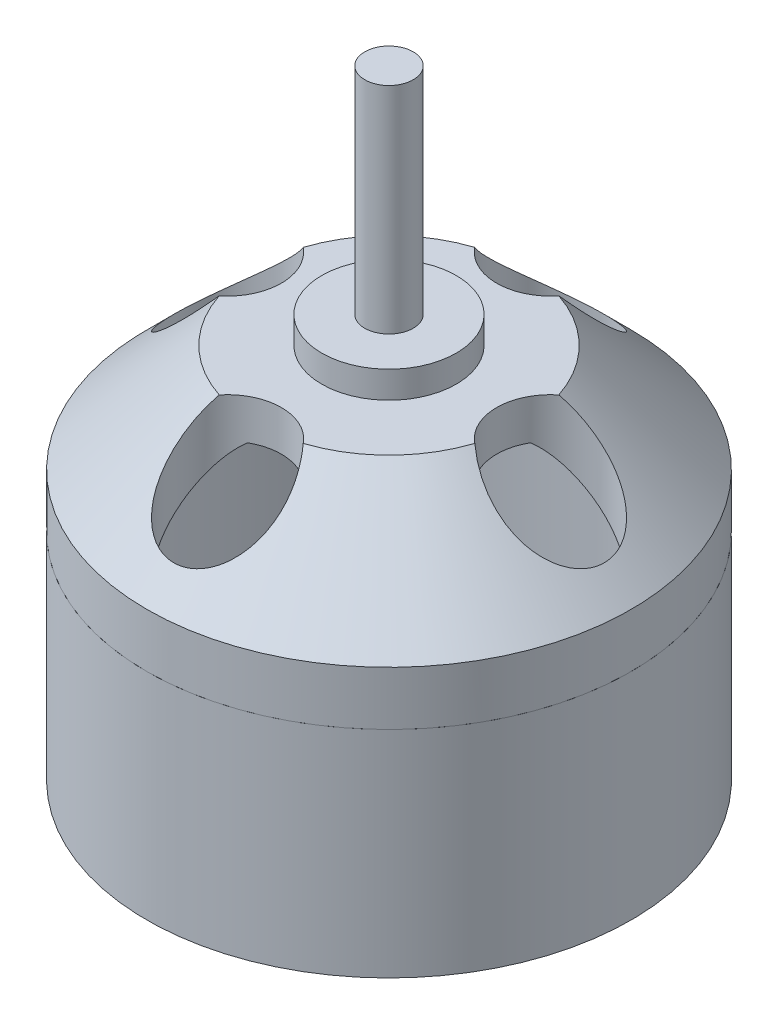
SolidWorks part; units mm, degrees
ref_plane "Ön Düzlem" through (0, 0, 0) normal (0, 0, 1) x (1, 0, 0)
ref_plane "Üst Düzlem" through (0, 0, 0) normal (0, 1, 0) x (1, 0, 0)
ref_plane "Sağ Düzlem" through (0, 0, 0) normal (1, 0, 0) x (0, 0, -1)
sketch "Çizim2" plane through (0, 0, 0) normal (0, 1, 0) x (1, 0, 0)
  circle A0 centre (0, 0) radius 9
  dimension "D1" = 18
extrude "Yükseklik-Ekstrüzyon1" add sketch "Çizim2" along normal blind 1
sketch "Çizim3" plane through (0, 1, 0) normal (0, 1, 0) x (1, 0, 0)
  circle A1 centre (0, 0) radius 9
  circle A2 centre (0, 0) radius 9
  dimension "D1" = 0
extrude "Yükseklik-Ekstrüzyon2" add sketch "Çizim3" along normal blind 5
chamfer "Pah1" distance 4 angle 45 1 edges at (0, 6, 9)
shell "İç Boşaltma1" thickness 1.5 removed face at (0, 0, 9)
sketch "Çizim5" plane through (0, 6, 0) normal (0, 1, 0) x (1, 0, 0)
  circle A0 centre (0, -6) radius 2
  circle A1 centre (-6, 0) radius 2
  circle A2 centre (0, 6) radius 2
  circle A3 centre (6, 0) radius 2
  point P12 (0, 0)
  dimension "D2" = 4
  dimension "D1" = 6
  dimension "D3" = 4
extrude "Kes-Ekstrüzyon1" cut sketch "Çizim5" against normal blind 6
sketch "Çizim6" plane through (0, 0, 0) normal (0, -1, 0) x (1, 0, 0)
  circle A0 centre (0, 0) radius 9
  circle A1 centre (0, 0) radius 8.5
  dimension "D1" = 17
  dimension "D2" = 18
sketch "Çizim7" plane through (0, 6, 0) normal (0, 1, 0) x (1, 0, 0)
  circle A0 centre (0, 0) radius 2.5
  dimension "D1" = 5
extrude "Yükseklik-Ekstrüzyon4" add sketch "Çizim7" along normal blind 1
sketch "Çizim8" plane through (0, 7, 0) normal (0, 1, 0) x (1, 0, 0)
  circle A0 centre (0, 0) radius 0.9
  dimension "D1" = 1.8
extrude "Yükseklik-Ekstrüzyon6" add sketch "Çizim6" along normal blind 8 separate body
extrude "Yükseklik-Ekstrüzyon7" add sketch "Çizim8" along normal blind 8 and the other way blind 20 separate body
